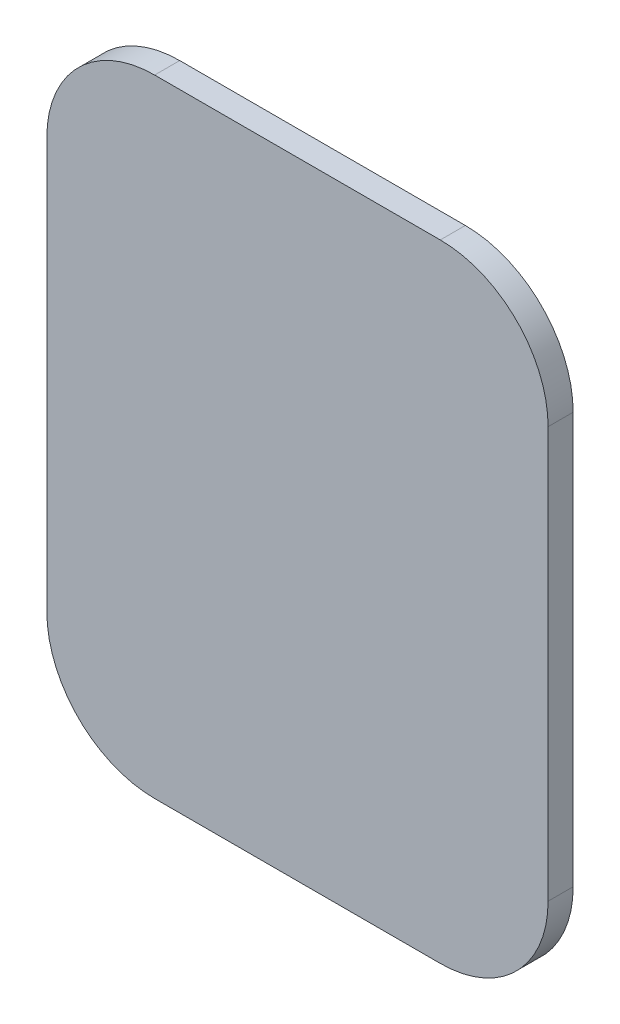
SolidWorks part; units mm, degrees
ref_plane "mating-plane" through (0, 0, 0) normal (0, 0, 1) x (1, 0, 0)
ref_plane "Top Plane" through (0, 0, 0) normal (0, 1, 0) x (1, 0, 0)
ref_plane "Right Plane" through (0, 0, 0) normal (1, 0, 0) x (0, 0, -1)
ref_axis "axis" through (0, 0, -0.4622) along (0, 0, 1)
sketch "Sketch9" plane through (0, 0, 0) normal (0, 0, 1) x (1, 0, 0)
  line L0 (1, 0) -> (-1, 0) construction
  line L2 (0, 1.25) -> (0, -1.25) construction
  line L20 (1, 0.8198) -> (1, -0.8198)
  line L21 (0.5698, -1.25) -> (-0.5698, -1.25)
  line L22 (1, -0.8198) -> (0.5698, -0.8198) construction
  line L23 (0.5698, -0.8198) -> (0.5698, -1.25) construction
  line L24 (1, -0.8198) -> (1, -1.25) construction
  line L25 (1, -1.25) -> (0.5698, -1.25) construction
  line L26 (-1, -0.8198) -> (-1, 0.8198)
  line L27 (1, -1.25) -> (-1, -1.25) construction
  line L28 (1, -1.25) -> (1, 1.25) construction
  line L29 (1, 1.25) -> (-1, 1.25) construction
  line L30 (-1, -1.25) -> (-1, 1.25) construction
  line L31 (-0.5698, 1.25) -> (0.5698, 1.25)
  arc A1 (1, -0.8198) -> (0.5698, -1.25) centre (0.5698, -0.8198) cw
  arc A2 (-0.5698, -1.25) -> (-1, -0.8198) centre (-0.5698, -0.8198) cw
  arc A3 (-1, 0.8198) -> (-0.5698, 1.25) centre (-0.5698, 0.8198) cw
  arc A4 (0.5698, 1.25) -> (1, 0.8198) centre (0.5698, 0.8198) cw
extrude "landing-pad-2.5x2" add sketch "Sketch9" against normal blind 0.1 separate body
sketch "Sketch18" plane through (0, 0, 0) normal (0, 0, 1) x (1, 0, 0)
  line L0 (1, 0) -> (-1, 0) construction
  line L2 (0, 1) -> (0, -1) construction
  line L20 (1, 0.5698) -> (1, -0.5698)
  line L21 (0.5698, -1) -> (-0.5698, -1)
  line L22 (1, -0.5698) -> (0.5698, -0.5698) construction
  line L23 (0.5698, -0.5698) -> (0.5698, -1) construction
  line L24 (1, -0.5698) -> (1, -1) construction
  line L25 (1, -1) -> (0.5698, -1) construction
  line L26 (-1, -0.5698) -> (-1, 0.5698)
  line L27 (1, -1) -> (-1, -1) construction
  line L28 (1, -1) -> (1, 1) construction
  line L29 (1, 1) -> (-1, 1) construction
  line L30 (-1, -1) -> (-1, 1) construction
  line L31 (-0.5698, 1) -> (0.5698, 1)
  arc A1 (1, -0.5698) -> (0.5698, -1) centre (0.5698, -0.5698) cw
  arc A2 (-0.5698, -1) -> (-1, -0.5698) centre (-0.5698, -0.5698) cw
  arc A3 (-1, 0.5698) -> (-0.5698, 1) centre (-0.5698, 0.5698) cw
  arc A4 (0.5698, 1) -> (1, 0.5698) centre (0.5698, 0.5698) cw
extrude "landing-pad-2x2" [suppressed] add sketch "Sketch18" against normal blind 0.1 separate body
sketch "Sketch3" plane through (0, 0, 0) normal (0, 0, -1) x (-1, 0, 0)
  circle A0 centre (0, 0) radius 0.535
extrude "pin-body" [suppressed] add sketch "Sketch3" against normal blind 2.93 separate body
sketch "Sketch11" plane through (0, 0, 0) normal (0, 1, 0) x (1, 0, 0)
  line L0 (-0.005, 0) -> (-0.535, 0)
  line L2 (-0.535, 0) -> (-0.535, -0.53)
  arc A0 (-0.005, 0) -> (-0.535, -0.53) centre (-0.005, -0.53) ccw
revolve "dome" [suppressed] cut sketch "Sketch11" angle 360 about axis through (0, 0, -0.4622) along (0, 0, 1)
sketch "Sketch17" [suppressed] plane through (0, 0, 0) normal (0, 0, 1) x (1, 0, 0)
  line L1 (-7.7123, 1.2258) -> (6.7302, 1.2258)
  line L2 (-7.7123, 1.2258) -> (-7.7123, -1.8908)
  line L3 (-7.7123, -1.8908) -> (6.7302, -1.8908)
  line L4 (6.7302, 1.2258) -> (6.7302, -1.8908)
extrude "fake-thing" [suppressed] add sketch "Sketch17" along normal blind 0.7 separate body
sketch "Sketch8" [suppressed] plane through (0, 0, 0) normal (0, 0, -1) x (-1, 0, 0)
  circle A0 centre (0, 0) radius 0.749
  circle A1 centre (0, 0) radius 0.535
extrude "body-front" [suppressed] add sketch "Sketch8" against normal blind 3.81 from surface separate body
sketch "Sketch15" [suppressed] plane through (0, 0, 4.51) normal (0, 0, 1) x (1, 0, 0)
  circle A0 centre (0, 0) radius 0.535
extrude "plug" [suppressed] add sketch "Sketch15" against normal blind 0.75
sketch "Sketch13" [suppressed] plane through (0, 0, 4.51) normal (0, 0, 1) x (1, 0, 0)
  circle A1 centre (0, 0) radius 0.89
  circle A2 centre (0, 0) radius 0.749
extrude "body-back" [suppressed] add sketch "Sketch13" against normal blind 2
sketch "Sketch14" [suppressed] plane through (0, 0, 2.51) normal (0, 0, -1) x (-1, 0, 0)
  circle A0 centre (0, 0) radius 1.08
extrude "flange" [suppressed] add sketch "Sketch14" along normal blind 0.25
ref_plane "PCB-edge" [suppressed] through (0, 0, 2.51) normal (0, 0, 1) x (1, 0, 0)
sketch "Sketch16" [suppressed] plane through (0, 0, 0) normal (1, 0, 0) x (0, 0, -1)
  line L5 (-2.26, -1.08) -> (-2.26, 1.08) construction
  line L6 (-2.26, -0.749) -> (-2.45, -0.749) construction
  line L7 (-2.45, -0.749) -> (-2.1, -0.749)
  line L8 (-2.45, -0.749) -> (-2.45, -0.814)
  line L9 (-2.45, -0.814) -> (-2.1, -0.749)
revolve "rib" [suppressed] add sketch "Sketch16" angle 360 about axis through (0, 0, -0.4622) along (0, 0, 1)
